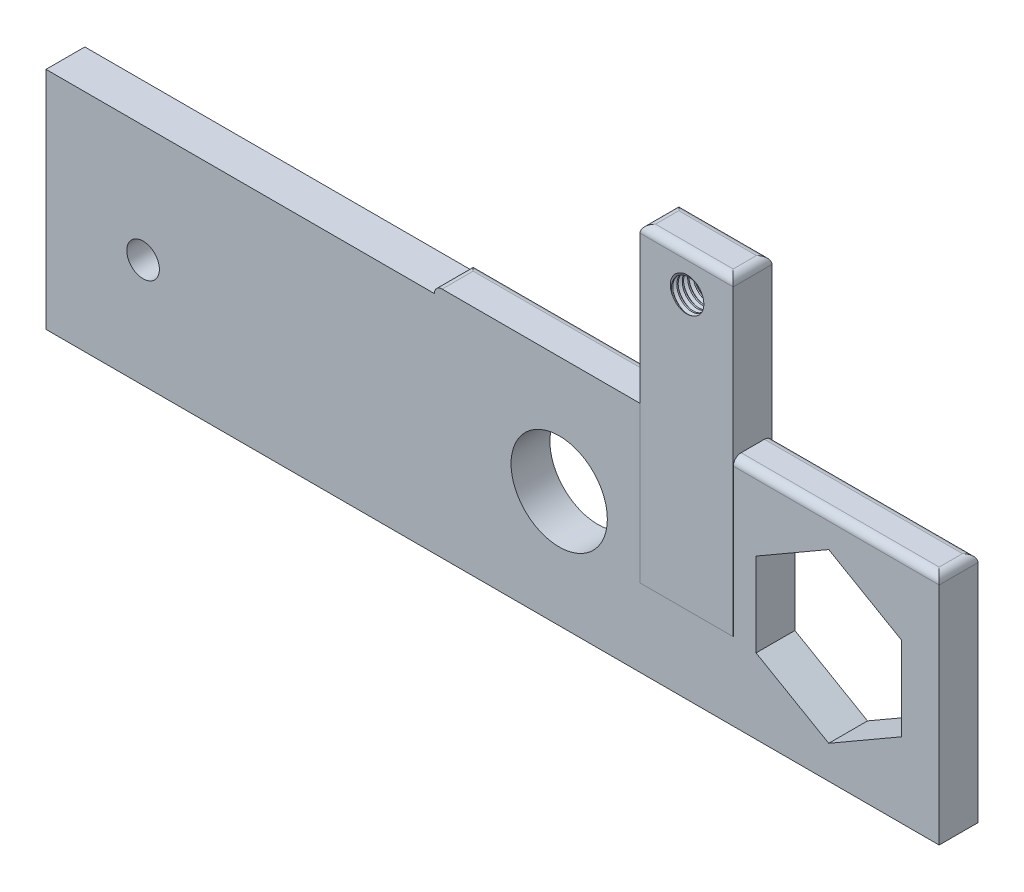
SolidWorks part; units mm, degrees
ref_plane "Front Plane" through (0, 0, 0) normal (0, 0, 1) x (1, 0, 0)
ref_plane "Top Plane" through (0, 0, 0) normal (0, 1, 0) x (1, 0, 0)
ref_plane "Right Plane" through (0, 0, 0) normal (1, 0, 0) x (0, 0, -1)
sketch "Sketch1" plane through (0, 0, 0) normal (0, 0, 1) x (1, 0, 0)
  line L1 (-32.5, 15) -> (32.5, 15)
  line L2 (-32.5, 15) -> (-32.5, -15)
  line L3 (-32.5, -15) -> (32.5, -15)
  line L4 (32.5, 15) -> (32.5, -15)
  line L5 (0, -15) -> (0, 15) construction
  line L6 (-32.5, 0) -> (32.5, 0) construction
  point P0 (0, 0)
  dimension "D1" = 30
  dimension "D2" = 65
extrude "Boss-Extrude1" add sketch "Sketch1" along normal blind 5
sketch "Sketch2" plane through (0, 0, 5) normal (0, 0, 1) x (1, 0, 0)
  line L4 (18.2794, -10.7603) -> (27.6325, -5.3603)
  line L5 (27.6325, -5.3603) -> (27.6325, 5.4397)
  line L6 (27.6325, 5.4397) -> (18.2794, 10.8397)
  line L7 (18.2794, 10.8397) -> (8.9263, 5.4397)
  line L8 (8.9263, 5.4397) -> (8.9263, -5.3603)
  line L9 (8.9263, -5.3603) -> (18.2794, -10.7603)
  circle A0 centre (-16.4237, -0.0241) radius 6.2
  dimension "D1" = 12.4
  dimension "D2" = 10.8
extrude "Cut-Extrude1" cut sketch "Sketch2" against normal blind 10
sketch "Sketch4" plane through (0, 15, 0) normal (0, 1, 0) x (1, 0, 0)
  line L8 (-6, -0.0243) -> (6, -0.0243)
  line L13 (-6, -0.0243) -> (-6, -5.0243)
  line L14 (-6, -5.0243) -> (6, -5.0243)
  line L15 (6, -0.0243) -> (6, -5.0243)
  line L16 (0, -5.0243) -> (0, -0.0243) construction
  line L17 (-6, -2.5243) -> (6, -2.5243) construction
  point P0 (0, -2.5243)
  point P6 (0, -2.5243)
  dimension "D1" = 5
  dimension "D2" = 12
extrude "Boss-Extrude5" add sketch "Sketch4" along normal mid plane 40
sketch "Sketch9" plane through (0, 0, 0) normal (0, 0, -1) x (-1, 0, 0)
  circle A0 centre (0, 30) radius 2
extrude "Cut-Extrude3" cut sketch "Sketch9" against normal mid plane 60
thread "Thread1" pitch 0.7 start angle 0, offset 1, length 10, pitch 0.7, diameter 4
ref_plane "Plane2" through (2, 30, -0.9757) normal (0, -1, 0) x (1, 0, 0)
sketch "Thread Profile2" plane through (2, 30, -0.9757) normal (0, -1, 0) x (1, 0, 0)
  line L0 (0, 0) -> (0, 0.7) construction
  line L1 (0, 0) -> (0.3789, 0.2187)
  line L2 (0.3789, 0.2187) -> (0.3789, 0.3062)
  line L3 (0.3789, 0.3062) -> (0, 0.525)
  line L4 (0.3789, 0.2625) -> (0, 0.2625) construction
  line L11 (0, 0) -> (0, 0.525)
  point P2 (0, 0)
  dimension "Pitch" = 0.7
  dimension "Profile_Angle" = 60
  dimension "Profile_Land" = 0.0875
  dimension "Profile_Height" = 0.3789
fillet "Fillet1" radius 1 8 edges at (0, 15, 0.0243) (6, 35, 2.5243) (0, 35, 0.0243) (-6, 35, 2.5243) (0, 35, 5.0243) (0, 15, 0) (-32.5, 15, 2.5) (32.5, 15, 2.5)
sketch "Sketch10" plane through (-32.5, 0, 0) normal (-1, 0, 0) x (0, 0, 1)
  line L1 (0, 14) -> (5, 14)
  line L2 (0, 14) -> (0, -15)
  line L3 (0, -15) -> (5, -15)
  line L4 (5, 14) -> (5, -15)
extrude "Boss-Extrude6" add sketch "Sketch10" along normal blind 50
sketch "Sketch11" plane through (0, 0, 5) normal (0, 0, 1) x (1, 0, 0)
  circle A0 centre (-70, -1) radius 2.1
extrude "Cut-Extrude4" cut sketch "Sketch11" against normal blind 50
